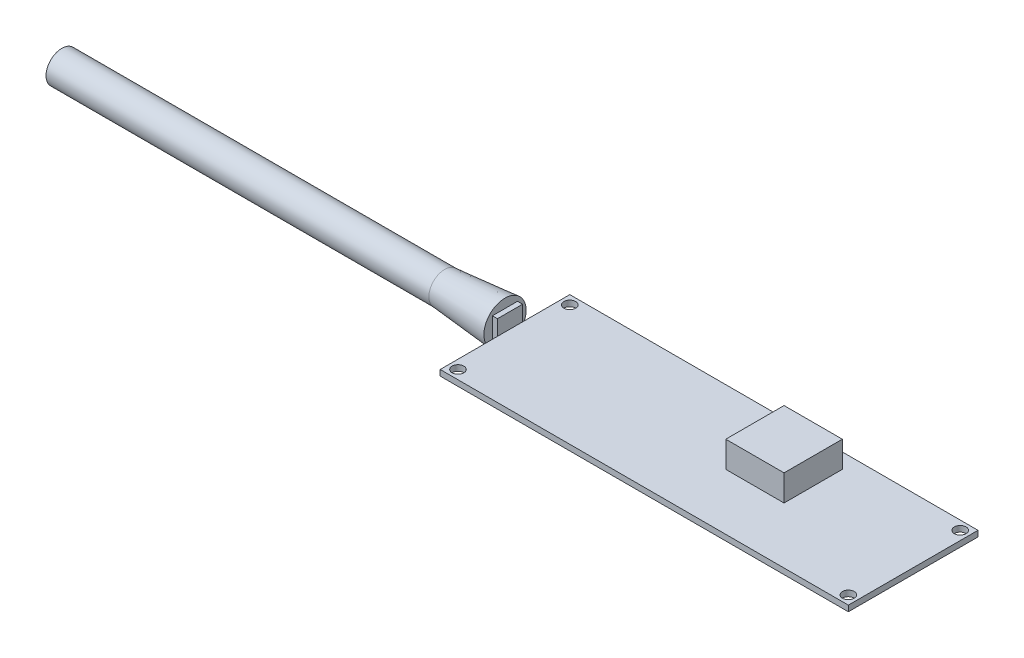
SolidWorks part; units mm, degrees
material "Glass Epoxy Composite"
ref_plane "Front Plane" through (0, 0, 0) normal (0, 0, 1) x (1, 0, 0)
ref_plane "Top Plane" through (0, 0, 0) normal (0, 1, 0) x (1, 0, 0)
ref_plane "Right Plane" through (0, 0, 0) normal (1, 0, 0) x (0, 0, -1)
sketch "Sketch1" plane through (0, 0, 0) normal (0, 1, 0) x (1, 0, 0)
  line L1 (-51.5874, -16.383) -> (51.5874, -16.383)
  line L2 (-51.5874, -16.383) -> (-51.5874, 16.383)
  line L3 (-51.5874, 16.383) -> (51.5874, 16.383)
  line L4 (51.5874, -16.383) -> (51.5874, 16.383)
  line L5 (-51.5874, -16.383) -> (51.5874, 16.383) construction
  line L6 (-51.5874, 16.383) -> (51.5874, -16.383) construction
  point P0 (0, 0)
  dimension "D1" = 103.1748
  dimension "D2" = 32.766
extrude "TRS PCB" add sketch "Sketch1" along normal blind 1.4605
sketch "Sketch2" plane through (0, 1.4605, 0) normal (0, 1, 0) x (1, 0, 0)
  line L8 (49.3395, -14.1351) -> (49.3395, 14.1351)
  line L9 (49.3395, 14.1351) -> (-49.3395, 14.1351)
  line L10 (-49.3395, 14.1351) -> (-49.3395, -14.1351)
  line L11 (-49.3395, -14.1351) -> (49.3395, -14.1351)
  line L12 (49.3395, -14.1351) -> (49.3395, 14.1351) construction
  line L13 (49.3395, 14.1351) -> (-49.3395, 14.1351) construction
  line L14 (-49.3395, 14.1351) -> (-49.3395, -14.1351) construction
  line L15 (-49.3395, -14.1351) -> (49.3395, -14.1351) construction
  circle A0 centre (-49.3395, 14.1351) radius 1.4859
  circle A1 centre (49.3395, 14.1351) radius 1.4859
  circle A2 centre (49.3395, -14.1351) radius 1.4859
  circle A3 centre (-49.3395, -14.1351) radius 1.4859
  dimension "D2" = 2.9718
  dimension "D1" = 2.2479
extrude "Stand off holes " cut sketch "Sketch2" against normal up to surface (1.4605 mm away) up to face at (0, 0, 0)
sketch "Sketch3" plane through (0, 1.4605, 0) normal (0, 1, 0) x (1, 0, 0)
  line L0 (51.5874, 16.383) -> (-51.5874, 16.383) construction
  line L1 (6.3754, 12.573) -> (21.1074, 12.573)
  line L2 (6.3754, 12.573) -> (6.3754, -2.159)
  line L3 (6.3754, -2.159) -> (21.1074, -2.159)
  line L4 (21.1074, 12.573) -> (21.1074, -2.159)
  line L5 (6.3754, 12.573) -> (21.1074, -2.159) construction
  line L6 (6.3754, -2.159) -> (21.1074, 12.573) construction
  line L8 (51.5874, -16.383) -> (51.5874, 16.383) construction
  point P0 (13.7414, 5.207)
  dimension "D1" = 14.732
  dimension "D2" = 14.732
  dimension "D3" = 3.81
  dimension "D4" = 30.48
extrude "GPS Antenna " add sketch "Sketch3" along normal blind 6.604
sketch "Sketch4" plane through (-51.5874, 0, 0) normal (-1, 0, 0) x (0, 0, 1)
  line L0 (-16.383, 0) -> (16.383, 0) construction
  line L1 (-4.445, -0.762) -> (1.905, -0.762)
  line L2 (-4.445, -0.762) -> (-4.445, 5.334)
  line L3 (-4.445, 5.334) -> (1.905, 5.334)
  line L4 (1.905, -0.762) -> (1.905, 5.334)
  line L5 (-4.445, -0.762) -> (1.905, 5.334) construction
  line L6 (-4.445, 5.334) -> (1.905, -0.762) construction
  line L7 (16.383, 1.4605) -> (16.383, 0) construction
  point P0 (-1.27, 2.286)
  dimension "D1" = 6.35
  dimension "D2" = 6.096
  dimension "D3" = 0.762
  dimension "D4" = 14.478
extrude "Boss-Extrude2" add sketch "Sketch4" along normal blind 1.27
sketch "Sketch5" plane through (-52.8574, 0, 0) normal (-1, 0, 0) x (0, 0, 1)
  line L0 (-4.445, 5.334) -> (1.905, -0.762) construction
  line L1 (-4.445, -0.762) -> (1.905, 5.334) construction
  circle A0 centre (-1.27, 2.286) radius 5.334
  dimension "D1" = 10.668
extrude "Boss-Extrude3" add sketch "Sketch5" along normal blind 15.24 draft 5
sketch "Sketch6" plane through (-68.0974, 0, 0) normal (-1, 0, 0) x (0, 0, 1)
  circle A0 centre (-1.27, 2.286) radius 4.0005
  circle A1 centre (-1.27, 2.286) radius 4.0007 construction
  dimension "D1" = 8.001
extrude "Boss-Extrude4" add sketch "Sketch6" along normal blind 96.774
